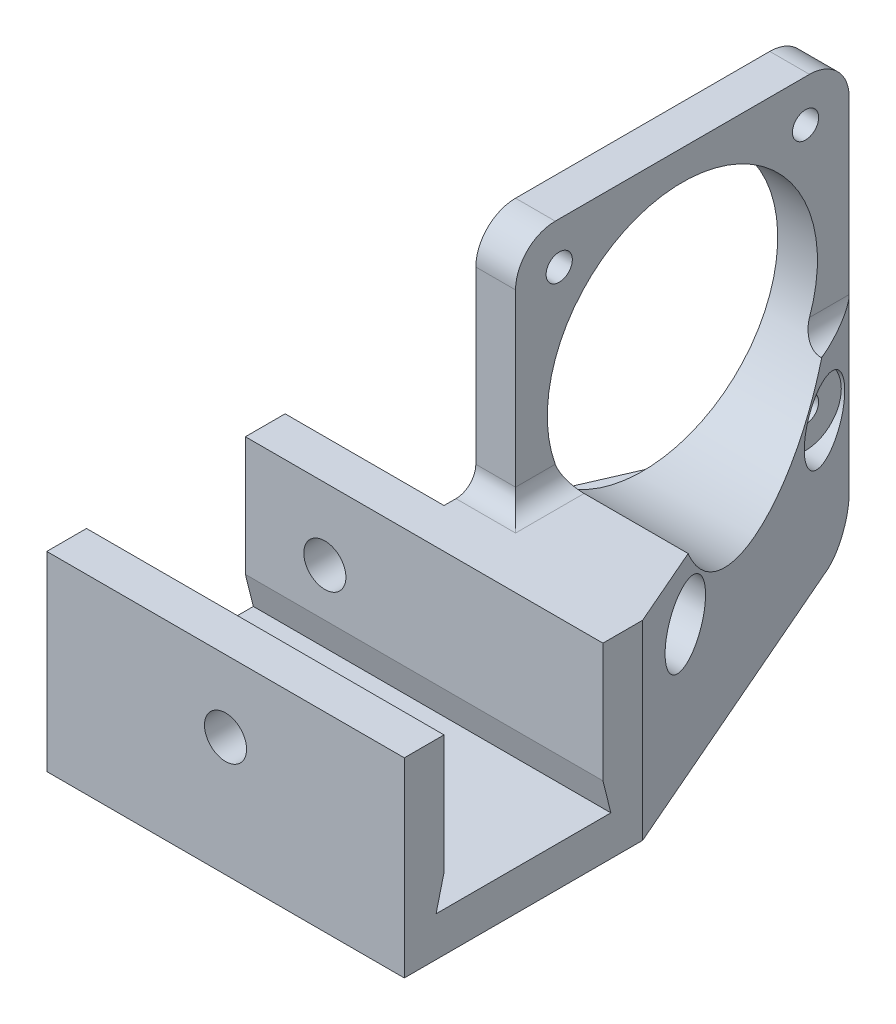
SolidWorks part; units mm, degrees
ref_plane "Front Plane" through (0, 0, 0) normal (0, 0, 1) x (1, 0, 0)
ref_plane "Top Plane" through (0, 0, 0) normal (0, 1, 0) x (1, 0, 0)
ref_plane "Right Plane" through (0, 0, 0) normal (1, 0, 0) x (0, 0, -1)
sketch "Sketch1" plane through (0, 0, 0) normal (0, 0, 1) x (1, 0, 0)
  line L1 (0, 0) -> (45, 0)
  line L2 (0, 0) -> (0, 24)
  line L3 (0, 24) -> (45, 24)
  line L4 (45, 0) -> (45, 24)
  dimension "D1" = 45
  dimension "D2" = 24
extrude "Boss-Extrude1" add sketch "Sketch1" along normal blind 5
sketch "Sketch2" plane through (0, 0, 0) normal (0, 0, -1) x (-1, 0, 0)
  line L1 (-25, 24) -> (-20, 24)
  line L2 (-25, 24) -> (-25, 0)
  line L3 (-25, 0) -> (-20, 0)
  line L4 (-20, 24) -> (-20, 0)
  line L5 (-45, 24) -> (0, 24) construction
  line L7 (0, 24) -> (0, 0) construction
  dimension "D1" = 5
  dimension "D2" = 20
extrude "Boss-Extrude2" add sketch "Sketch2" along normal blind 46
sketch "Sketch3" plane through (0, 0, 5) normal (0, 0, 1) x (1, 0, 0)
  line L0 (0, 24) -> (0, 0) construction
  line L1 (45, 0) -> (0, 0)
  line L2 (45, 0) -> (45, 5)
  line L3 (45, 5) -> (0, 5)
  line L4 (0, 0) -> (0, 5)
  dimension "D1" = 5
extrude "Boss-Extrude3" add sketch "Sketch3" along normal blind 20
chamfer "Chamfer2" distance 20 angle 66.5 1 edges at (25, 12, 0) first distance on face at (35, 12, 0)
chamfer "Chamfer3" distance 20 angle 66.5 1 edges at (20, 12, 0) first distance on face at (10, 12, 0)
sketch "Sketch4" plane through (0, 24, 0) normal (0, 1, 0) x (1, 0, 0)
  line L1 (20, 46) -> (25, 46)
  line L2 (20, 46) -> (20, 4)
  line L3 (20, 4) -> (25, 4)
  line L4 (25, 46) -> (25, 4)
  dimension "D1" = 42
  dimension "D2" = 5
extrude "Boss-Extrude4" add sketch "Sketch4" along normal blind 29
sketch "Sketch6" plane through (25, 0, 0) normal (1, 0, 0) x (0, 0, -1)
  line L1 (46, 0) -> (45.9969, 0) construction
  line L2 (46, 53) -> (46, 0) construction
  circle A0 centre (25, 32.24) radius 17
  dimension "D1" = 34
  dimension "D2" = 32.24
  dimension "D3" = 21
extrude "Cut-Extrude1" cut sketch "Sketch6" against normal through all both and the other way through all
sketch "Sketch7" plane through (20, 0, 0) normal (-1, 0, 0) x (0, 0, 1)
  line L1 (-46, 53) -> (0, 53)
  line L2 (-46, 53) -> (-46, 9)
  line L3 (-46, 9) -> (0, 9)
  line L4 (0, 53) -> (0, 9)
  line L5 (5, 24) -> (5, 5) construction
  dimension "D1" = 44
  dimension "D2" = 5
extrude "Cut-Extrude2" cut sketch "Sketch7" along normal through all
sketch "Sketch8" plane through (20, 0, 0) normal (-1, 0, 0) x (0, 0, 1)
  line L1 (-40.5, 16.74) -> (-9.5, 16.74) construction
  line L2 (-40.5, 16.74) -> (-40.5, 47.74) construction
  line L3 (-40.5, 47.74) -> (-9.5, 47.74) construction
  line L4 (-9.5, 16.74) -> (-9.5, 47.74) construction
  line L5 (-40.5, 16.74) -> (-9.5, 47.74) construction
  line L6 (-40.5, 47.74) -> (-9.5, 16.74) construction
  circle A0 centre (-40.5, 47.74) radius 1.65
  circle A1 centre (-9.5, 47.74) radius 1.65
  circle A2 centre (-9.5, 16.74) radius 1.65
  circle A3 centre (-40.5, 16.74) radius 1.65
  point P0 (-25, 32.24)
  dimension "D3" = 3.3
  dimension "D1" = 31
  dimension "D2" = 31
extrude "Cut-Extrude3" cut sketch "Sketch8" against normal through all
sketch "Sketch9" plane through (25, 0, 0) normal (1, 0, 0) x (0, 0, -1)
  circle A0 centre (9.5, 16.74) radius 4.5
  circle A1 centre (40.5, 16.74) radius 4.5
  dimension "D1" = 9
  dimension "D2" = 9
extrude "Cut-Extrude4" cut sketch "Sketch9" along normal through all
fillet "Fillet1" radius 5 3 edges at (22.5, 0, -46) (22.5, 53, -4) (22.5, 53, -46)
sketch "Sketch10" plane through (0, 0, 0) normal (0, -1, 0) x (1, 0, 0)
  line L0 (0, 25) -> (45, 25) construction
  line L1 (45, 25) -> (45, 0) construction
  circle A0 centre (22.5, 15) radius 2.65
  dimension "D2" = 5.3
  dimension "D1" = 10
  dimension "D3" = 22.5
extrude "Cut-Extrude5" cut sketch "Sketch10" against normal blind 10
sketch "Sketch11" plane through (0, 0, 5) normal (0, 0, 1) x (1, 0, 0)
  line L0 (45, 5) -> (0, 5) construction
  line L1 (0, 24) -> (0, 5) construction
  circle A0 centre (10, 15) radius 2.65
  dimension "D2" = 5.3
  dimension "D1" = 10
  dimension "D3" = 10
extrude "Cut-Extrude6" cut sketch "Sketch11" against normal blind 10
sketch "Sketch12" plane through (0, 0, 0) normal (0, 1, 0) x (1, 0, 0)
  line L1 (45, -25) -> (0, -25)
  line L2 (45, -25) -> (45, -30)
  line L3 (45, -30) -> (0, -30)
  line L4 (0, -25) -> (0, -30)
  dimension "D1" = 5
extrude "Boss-Extrude5" add sketch "Sketch12" along normal blind 24
sketch "Sketch13" plane through (0, 0, 30) normal (0, 0, 1) x (1, 0, 0)
  line L1 (45, 24) -> (45, 0) construction
  line L2 (0, 0) -> (45, 0) construction
  circle A0 centre (22.5, 15) radius 2.65
  dimension "D1" = 5.3
  dimension "D2" = 15
  dimension "D3" = 22.5
extrude "Cut-Extrude7" cut sketch "Sketch13" against normal blind 10
sketch "Sketch14" plane through (45, 0, 0) normal (1, 0, 0) x (0, 0, -1)
  line L0 (-25, 5) -> (-26, 5)
  line L1 (-26, 5) -> (-25, 9)
  line L2 (-25, 24) -> (-25, 5) construction
  line L3 (-25, 9) -> (-25, 5)
  line L4 (-5, 5) -> (-4, 5)
  line L5 (-4, 5) -> (-5, 9)
  line L6 (-5, 5) -> (-5, 24) construction
  line L7 (-5, 9) -> (-5, 5)
  dimension "D1" = 1
  dimension "D5" = 4
  dimension "D6" = 1
  dimension "D7" = 4
extrude "Cut-Extrude8" cut sketch "Sketch14" against normal through all both and the other way through all
fillet "Fillet2" radius 2.5 3 edges at (25, 24, -42.9332) (25, 24, -7.0652) (22.5, 24, -4)
